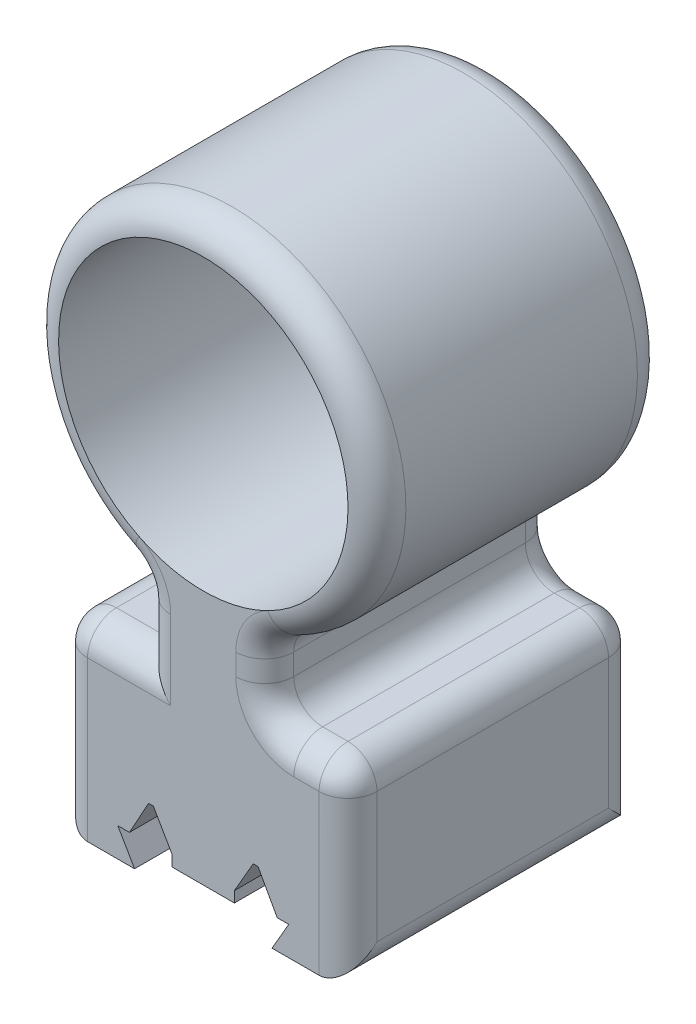
SolidWorks part; units mm, degrees
material "6061-T4 (SS)"
ref_plane "Front Plane" through (0, 0, 0) normal (0, 0, 1) x (1, 0, 0)
ref_plane "Top Plane" through (0, 0, 0) normal (0, 1, 0) x (1, 0, 0)
ref_plane "Right Plane" through (0, 0, 0) normal (1, 0, 0) x (0, 0, -1)
sketch "Sketch1" plane through (0, 0, 0) normal (0, 0, 1) x (1, 0, 0)
  line L0 (-4.75, -1.402) -> (-10, -1.402)
  line L1 (4.75, -1.402) -> (10, -1.402)
  line L2 (0, -1001.402) -> (0, 48998.598) construction
  line L3 (3.7786, 3) -> (3.4528, 3)
  line L4 (3.4528, 3) -> (2.1514, 0.7461)
  line L5 (5.1059, 0.6) -> (3.7786, 3)
  line L6 (-3.7786, 3) -> (-5.1059, 0.6)
  line L7 (-2.1514, 0.7461) -> (-3.4528, 3)
  line L8 (-3.4528, 3) -> (-3.7786, 3)
  line L9 (-5.9059, 0.6) -> (-4.75, -1.402)
  line L10 (4.75, -1.402) -> (5.9059, 0.6)
  line L11 (5.9059, 0.6) -> (5.1059, 0.6)
  line L12 (2.1514, 0.7461) -> (2.1514, 0)
  line L13 (2.1514, 0) -> (-2.1514, 0)
  line L14 (-2.1514, 0) -> (-2.1514, 0.7461)
  line L15 (-5.1059, 0.6) -> (-5.9059, 0.6)
  line L16 (-10, -1.402) -> (-10, 11.598)
  line L17 (-10, 11.598) -> (-4.25, 11.598)
  line L18 (-4.25, 11.598) -> (-4.25, 16.3758)
  line L19 (4.75, -1.402) -> (10, -1.402)
  line L20 (10, -1.402) -> (10, 11.598)
  line L21 (10, 11.598) -> (4.25, 11.598)
  line L22 (4.25, 11.598) -> (4.25, 16.3758)
  circle A0 centre (0, 27.598) radius 10
  arc A1 (4.25, 16.3758) -> (-4.25, 16.3758) centre (0, 27.598) ccw
  point P18 (0, 0)
  dimension "D11" = 20
  dimension "D12" = 24
  dimension "D1" = 2.002
  dimension "D2" = 0.7461
  dimension "D3" = 0.8
  dimension "D4" = 9.5
  dimension "D5" = 11.8117
  dimension "D6" = 4.3029
  dimension "D7" = 0.3258
  dimension "D8" = 60
  dimension "D9" = 1.402
  dimension "D10" = 2.4
  dimension "D13" = 13
  dimension "D14" = 16
  dimension "D15" = 4.25
  dimension "D16" = 5.75
extrude "Boss-Extrude1" add sketch "Sketch1" along normal mid plane 20 contours L13 L2 A0 A1 L18 L17 L16 L0 L9 L15 L6 L8 L7 L14 | L2 L13 L12 L4 L3 L5 L11 L10 L1 L20 L21 L22 A1 A0 region at (-7.375, -0.9748, 0) region at (11.3837, 29.6814, 0)
fillet "Fillet1" radius 2 21 edges at (0, 39.598, -10) (4.25, 13.9869, -10) (-10, 11.598, 0) (-4.25, 16.3758, 0) (-10, 5.098, -10) (-7.125, 11.598, -10) (-4.25, 13.9869, -10) (4.25, 16.3758, 0) (4.25, 11.598, 0) (7.125, 11.598, -10) (10, 5.098, -10) (10, 11.598, 0) (10, 5.098, 10) (-10, 5.098, 10) (-7.125, 11.598, 10) (7.125, 11.598, 10) (4.25, 13.9869, 10) (-4.25, 13.9869, 10) (0, 39.598, 10) (10, -1.402, 0) (-10, -1.402, 0)
